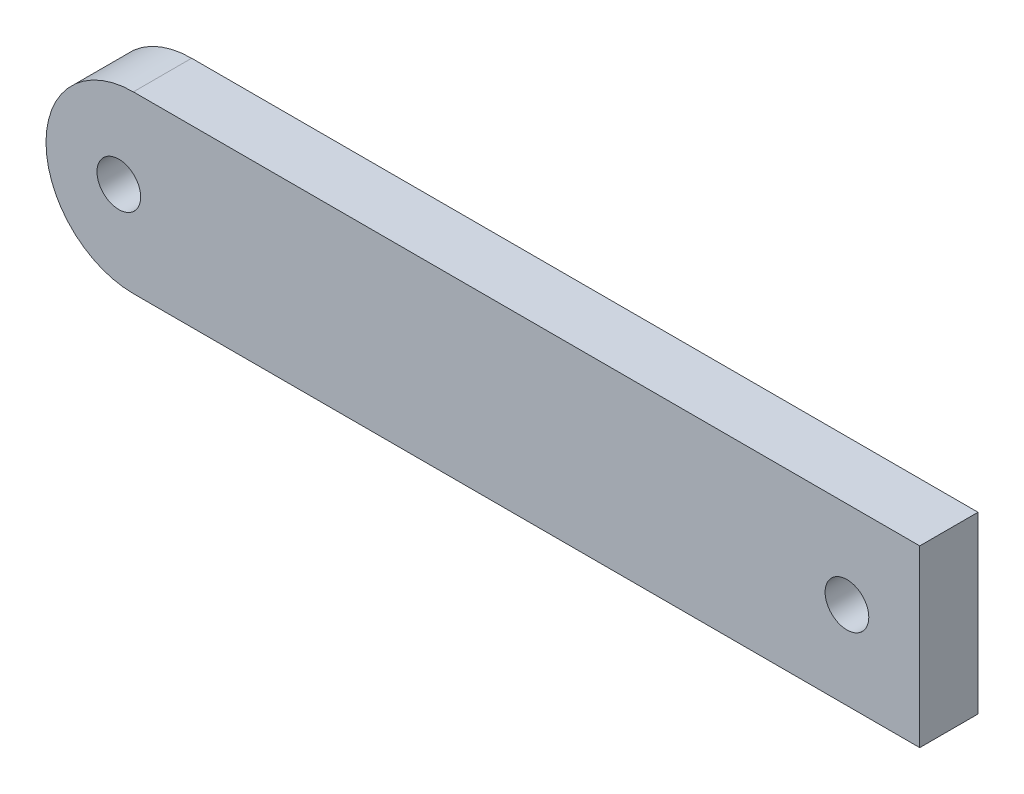
SolidWorks part; units mm, degrees
ref_plane "前视基准面" through (0, 0, 0) normal (0, 0, 1) x (1, 0, 0)
ref_plane "上视基准面" through (0, 0, 0) normal (0, 1, 0) x (1, 0, 0)
ref_plane "右视基准面" through (0, 0, 0) normal (1, 0, 0) x (0, 0, -1)
sketch "草图1" plane through (0, 0, 0) normal (0, 0, 1) x (1, 0, 0)
  line L1 (35, -6) -> (-25, -6)
  line L2 (35, -6) -> (35, 6)
  line L3 (35, 6) -> (-25, 6)
  line L4 (-25, -6) -> (-25, 6)
  circle A0 centre (-20, 0) radius 1.5
  circle A1 centre (30, 0) radius 1.5
  point P0 (0, 0)
  point P6 (0, 0)
extrude "凸台-拉伸1" add sketch "草图1" along normal blind 4
fillet "圆角1" radius 6 2 edges at (-25, -6, 2) (-25, 6, 2)
